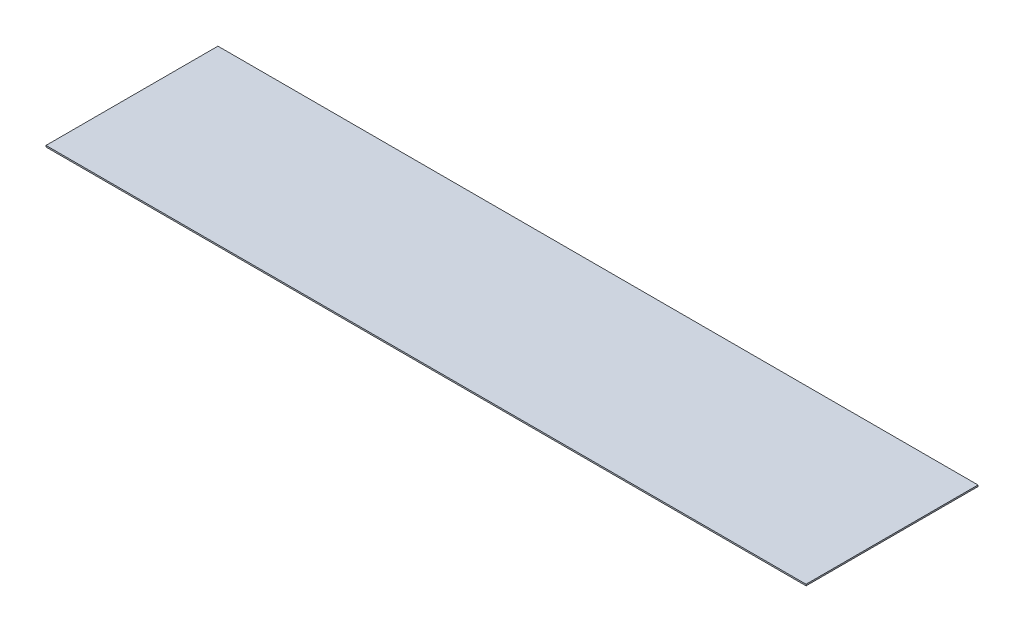
SolidWorks part; units mm, degrees
material "Natural Rubber"
ref_plane "Front" through (0, 0, 0) normal (0, 0, 1) x (1, 0, 0)
ref_plane "Top" through (0, 0, 0) normal (0, 1, 0) x (1, 0, 0)
ref_plane "Right" through (0, 0, 0) normal (1, 0, 0) x (0, 0, -1)
sketch "Sketch1" plane through (0, 0, 0) normal (0, 1, 0) x (1, 0, 0)
  line L1 (-1447.8, 825.5) -> (1447.8, 825.5)
  line L2 (-1447.8, 825.5) -> (-1447.8, -825.5)
  line L3 (-1447.8, -825.5) -> (1447.8, -825.5)
  line L4 (1447.8, 825.5) -> (1447.8, -825.5)
  line L5 (-1447.8, 825.5) -> (1447.8, -825.5) construction
  line L6 (-1447.8, -825.5) -> (1447.8, 825.5) construction
  point P0 (0, 0)
  dimension "D1" = 2895.6
  dimension "D2" = 1651
extrude "Boss-Extrude1" [suppressed] add sketch "Sketch1" along normal blind 1473.2
sketch "Sketch2" [suppressed] plane through (0, 0, 0) normal (0, -1, 0) x (1, 0, 0)
  line L0 (0, 0) -> (2162.175, 0) construction
  line L1 (1447.8, 825.5) -> (1447.8, -825.5) construction
  line L2 (1752.6, 663.575) -> (2571.75, 663.575)
  line L3 (1752.6, 663.575) -> (1752.6, -663.575)
  line L4 (1752.6, -663.575) -> (2571.75, -663.575)
  line L5 (2571.75, 663.575) -> (2571.75, -663.575)
  line L6 (1752.6, 663.575) -> (2571.75, -663.575) construction
  line L7 (1752.6, -663.575) -> (2571.75, 663.575) construction
  dimension "D1" = 1327.15
  dimension "D2" = 819.15
  dimension "D3" = 304.8
extrude "Boss-Extrude2" [suppressed] add sketch "Sketch2" against normal blind 736.6 separate body
sketch "Sketch3" plane through (0, 0, 0) normal (0, 1, 0) x (-1, 0, 0)
  line L2 (6127.75, 914.4) -> (-6127.75, 914.4)
  line L3 (6127.75, 914.4) -> (6127.75, -914.4)
  line L4 (6127.75, -914.4) -> (-6127.75, -914.4)
  line L5 (-6127.75, 914.4) -> (-6127.75, -914.4)
  line L6 (6127.75, 914.4) -> (-6127.75, -914.4) construction
  line L7 (6127.75, -914.4) -> (-6127.75, 914.4) construction
  dimension "D1" = 1828.8
  dimension "D2" = 12255.5
extrude "Boss-Extrude3" add sketch "Sketch3" along normal blind 304.8 separate body
sketch "Sketch4" plane through (0, 304.8, 0) normal (0, 1, 0) x (1, 0, 0)
  line L0 (6127.75, -914.4) -> (6127.75, 914.4) construction
  line L1 (-6737.35, 1524) -> (6737.35, 1524)
  line L2 (-6737.35, 1524) -> (-6737.35, -1524)
  line L3 (-6737.35, -1524) -> (6737.35, -1524)
  line L4 (6737.35, 1524) -> (6737.35, -1524)
  line L5 (-6737.35, 1524) -> (6737.35, -1524) construction
  line L6 (-6737.35, -1524) -> (6737.35, 1524) construction
  line L7 (-6127.75, -914.4) -> (6127.75, -914.4) construction
  point P0 (0, 0)
  dimension "D1" = 609.6
  dimension "D2" = 609.6
extrude "Boss-Extrude4" add sketch "Sketch4" along normal blind 25.4 separate body
sketch "Sketch5" plane through (0, 304.8, 0) normal (0, -1, 0) x (1, 0, 0)
  line L0 (6127.75, -914.4) -> (-6127.75, -914.4) construction
  line L1 (-2940.05, -1308.1) -> (-3028.95, -1308.1)
  line L2 (-2940.05, -1308.1) -> (-2940.05, -1219.2)
  line L3 (-2940.05, -1219.2) -> (-3028.95, -1219.2)
  line L4 (-3028.95, -1308.1) -> (-3028.95, -1219.2)
  line L5 (-2940.05, -1308.1) -> (-3028.95, -1219.2) construction
  line L6 (-2940.05, -1219.2) -> (-3028.95, -1308.1) construction
  line L7 (-6127.75, -914.4) -> (-6127.75, 914.4) construction
  point P0 (-2984.5, -1263.65)
  dimension "D1" = 88.9
  dimension "D2" = 88.9
  dimension "D3" = 304.8
  dimension "D4" = 3098.8
extrude "Boss-Extrude5" add sketch "Sketch5" along normal blind 1219.2 separate body
chamfer "Chamfer1" distance 44.45 angle 45 4 edges at (-2984.5, -914.4, -1308.1) (-3028.95, -914.4, -1263.65) (-2984.5, -914.4, -1219.2) (-2940.05, -914.4, -1263.65)
